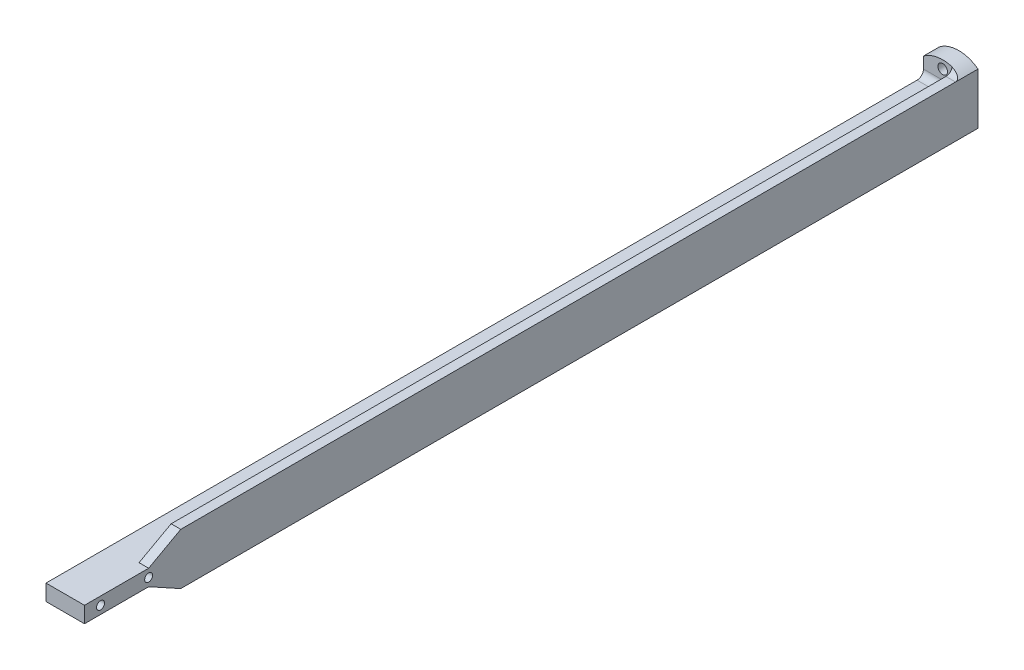
SolidWorks part; units mm, degrees
ref_plane "Plan de face" through (0, 0, 0) normal (0, 0, 1) x (1, 0, 0)
ref_plane "Plan de dessus" through (0, 0, 0) normal (0, 1, 0) x (1, 0, 0)
ref_plane "Plan de droite" through (0, 0, 0) normal (1, 0, 0) x (0, 0, -1)
sketch "Esquisse1" plane through (0, 0, 0) normal (0, 0, 1) x (1, 0, 0)
  line L0 (0, 0) -> (16.7354, 0) construction
  line L2 (12, 16) -> (12, -16)
  line L3 (12, -16) -> (-12, -16) construction
  line L4 (-12, -16) -> (-12, 16)
  line L5 (0, 0) -> (0, 15) construction
  circle A0 centre (0, 15) radius 3
  circle A1 centre (0, -15) radius 3
  circle A2 centre (0, 0) radius 20 construction
  arc A3 (-12, -16) -> (12, -16) centre (0, 0) ccw
  arc A4 (12, 16) -> (-12, 16) centre (0, 0) ccw
  dimension "D1" = 6
  dimension "D3" = 40
  dimension "D2" = 30
  dimension "D4" = 12
extrude "Boss.-Extru.1" add sketch "Esquisse1" along normal blind 10
sketch "Esquisse2" plane through (0, 0, 10) normal (0, 0, 1) x (1, 0, 0)
  line L0 (12, 16) -> (12, -16)
  line L1 (12, -16) -> (6, -16)
  line L2 (6, -16) -> (6, -5)
  line L3 (6, -5) -> (-12, -5)
  line L4 (-12, 16) -> (-12, -16) construction
  line L5 (-12, -5) -> (-12, 5)
  line L6 (-12, 5) -> (6, 5)
  line L7 (6, 5) -> (6, 16)
  line L8 (6, 16) -> (12, 16)
  dimension "D1" = 6
  dimension "D2" = 10
extrude "Boss.-Extru.2" add sketch "Esquisse2" along normal blind 547
sketch "Esquisse3" plane through (6, 0, 0) normal (-1, 0, 0) x (0, 0, 1)
  line L0 (557, 5) -> (557, 16)
  line L1 (557, 16) -> (497, 16)
  line L2 (557, 16) -> (10, 16) construction
  line L3 (497, 16) -> (517, 5)
  line L4 (557, 5) -> (10, 5) construction
  line L5 (517, 5) -> (557, 5)
  line L7 (557, -5) -> (557, -16)
  line L8 (557, -16) -> (497, -16)
  line L9 (557, -16) -> (10, -16) construction
  line L10 (497, -16) -> (517, -5)
  line L11 (557, -5) -> (10, -5) construction
  line L12 (517, -5) -> (557, -5)
  dimension "D1" = 40
  dimension "D2" = 60
extrude "Enlèv. mat.-Extru.1" cut sketch "Esquisse3" against normal through all
fillet "Congé1" radius 4 4 edges at (-3, 5, 10) (-3, -5, 10) (9, 16, 10) (9, -16, 10)
sketch "Esquisse4" plane through (-12, 0, 0) normal (-1, 0, 0) x (0, 0, 1)
  line L0 (557, 0) -> (268.6319, 0) construction
  line L1 (557, 5) -> (557, -5) construction
  circle A0 centre (547, 0) radius 2.5
  circle A1 centre (517, 0) radius 2.5
  dimension "D1" = 5
  dimension "D2" = 30
  dimension "D3" = 10
extrude "Enlèv. mat.-Extru.2" cut sketch "Esquisse4" against normal blind 12
extrude "Enlèv. mat.-Extru.3" cut sketch "Esquisse4<2>" along normal blind 12 from surface starting at face at (12, 0, 317)
sketch "Esquisse4<2>" plane through (-12, 0, 0) normal (-1, 0, 0) x (0, 0, 1) same geometry as "Esquisse4"
